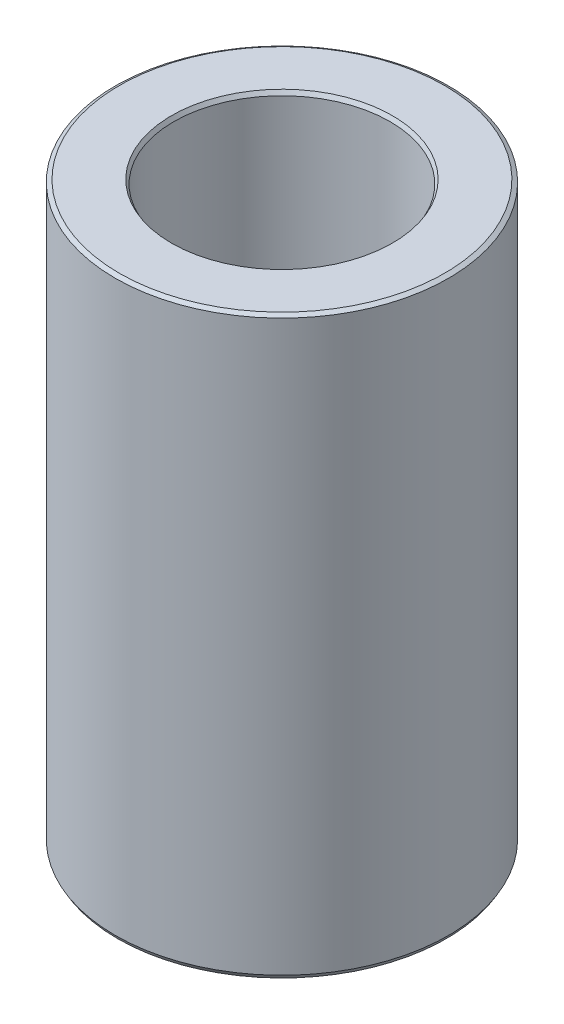
SolidWorks part; units mm, degrees
ref_plane "Front Plane" through (0, 0, 0) normal (0, 0, 1) x (1, 0, 0)
ref_plane "Top Plane" through (0, 0, 0) normal (0, 1, 0) x (1, 0, 0)
ref_plane "Right Plane" through (0, 0, 0) normal (1, 0, 0) x (0, 0, -1)
sketch "Sketch1" plane through (0, 0, 0) normal (0, 1, 0) x (1, 0, 0)
  circle A0 centre (0, 0) radius 55
  dimension "SLEEVE_OD" = 110
extrude "Boss-Extrude1" add sketch "Sketch1" along normal blind 189.9134
sketch "Sketch2" plane through (0, 0, 0) normal (0, 1, 0) x (1, 0, 0)
  circle A0 centre (0, 0) radius 35.6886
  dimension "BORE_D" = 71.3772
extrude "Cut-Extrude1" cut sketch "Sketch2" along normal through all
chamfer "Chamfer1" distance 0.7666 angle 60 4 edges at (0, 189.9134, 35.6886) (0, 0, 35.6886) (0, 0, 55) (0, 189.9134, 55) first distance on face at (0, 189.9134, 35.6886) first distance on face at (0, 0, 35.6886) first distance on face at (0, 189.9134, 55)
